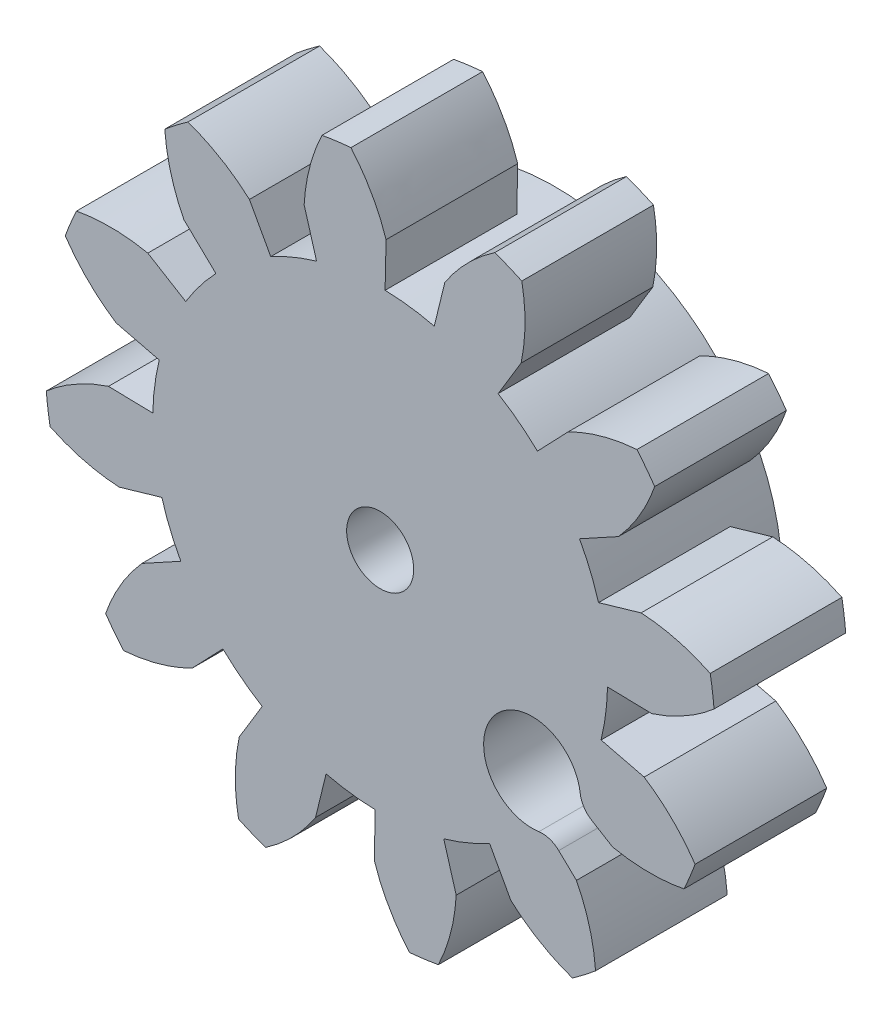
SolidWorks part; units mm, degrees
material "ABS"
ref_plane "Front Plane" through (0, 0, 0) normal (0, 0, 1) x (1, 0, 0)
ref_plane "Top Plane" through (0, 0, 0) normal (0, 1, 0) x (1, 0, 0)
ref_plane "Right Plane" through (0, 0, 0) normal (1, 0, 0) x (0, 0, -1)
sketch "Sketch1" plane through (0, 0, 0) normal (0, 0, 1) x (1, 0, 0)
  line L0 (0, 0) -> (0, 91.8742) construction
  line L1 (-88.8926, 12) -> (81.6756, 12) construction
  line L2 (-69.7625, -13.3915) -> (55.1169, 32.0609) construction
  line L3 (0, 0) -> (-3.8567, 10.5963) construction
  line L4 (0, 0) -> (-11.7377, 89.157) construction
  line L5 (1.5476, 11.1696) -> (0.2461, 11.3499) construction
  line L6 (-8.3652, 7.5617) -> (-1.9324, 14.678) construction
  circle A0 centre (0, 0) radius 12 construction
  circle A1 centre (0, 0) radius 11.2763 construction
  circle A2 centre (0, 0) radius 14 construction
  circle A3 centre (0, 0) radius 9.5 construction
  point P6 (0, 12)
  dimension "D1" = 24
  dimension "D2" = 20
  dimension "D3" = 4.1042
  dimension "D4" = 7.5
  dimension "D5" = 2
  dimension "D6" = 2.5
  dimension "D9" = 9.5929
  dimension "D10" = 1.3139
  dimension "D7" = 5.4886
  dimension "D8" = 5.4886
sketch "Sketch2" plane through (0, 0, 0) normal (0, 0, 1) x (1, 0, 0)
  circle A0 centre (0, 0) radius 9.5 construction
  circle A1 centre (0, 0) radius 9.5
extrude "Gear Body" add sketch "Sketch2" along normal mid plane 5.5
sketch "Sketch3" plane through (0, 0, 0) normal (0, 0, 1) x (1, 0, 0)
  line L0 (0.2461, 11.3499) -> (0, 0) construction
  line L1 (0.2461, 11.3499) -> (0.2059, 9.4978)
  line L4 (-1.9324, 14.678) -> (0, 0) construction
  line L5 (-3.1753, 10.8995) -> (-2.6571, 9.1208)
  circle A2 centre (0, 0) radius 9.5 construction
  arc A3 (0.2059, 9.4978) -> (-2.6571, 9.1208) centre (0, 0) ccw
  spline S0 degree 2 poles (-1.9324, 14.678) (-0.3812, 13.2624) (0.2461, 11.3499) knots 0 0 0 1 1 1
  spline S1 degree 2 poles (-1.9324, 14.678) (-3.0644, 12.9092) (-3.1753, 10.8995) knots 0 0 0 1 1 1
extrude "Gear Tooth" add sketch "Sketch3" along normal mid plane 5.5
pattern_circular "Tooth Pattern" count 12 over 360 about axis through (0, 0, 2.75) along (0, 0, -1) of "Gear Tooth"
sketch "Sketch4" plane through (0, 0, 2.75) normal (0, 0, 1) x (1, 0, 0)
  line L0 (-8.3652, 7.5617) -> (-1.9324, 14.678) construction
  line L1 (-8.3652, 7.5617) -> (-1.9324, 14.678) construction
  circle A0 centre (0, 0) radius 14 construction
  circle A1 centre (0, 0) radius 14
  circle A2 centre (0, 0) radius 14.8047
  point P3 (-1.9324, 14.678)
extrude "Tooth Outer Clean" cut sketch "Sketch4" against normal through all
sketch "Sketch5" plane through (0, 0, 2.75) normal (0, 0, 1) x (1, 0, 0)
  line L0 (0, 0) -> (0, 29.0711) construction
  line L1 (0, 0) -> (-31.2479, 0) construction
  circle A1 centre (0, 0) radius 1.4
  dimension "D2" = 2.8
extrude "Cut-Extrude1" cut sketch "Sketch5" against normal through all
sketch "Sketch7" plane through (0, 0, -2.75) normal (0, 0, -1) x (-1, 0, 0)
  circle A0 centre (0, 0) radius 4.15
  dimension "D1" = 8.3
extrude "Cut-Extrude3" cut sketch "Sketch7" against normal blind 0.2
sketch "Sketch9" plane through (0, 0, -2.75) normal (0, 0, -1) x (-1, 0, 0)
  circle A0 centre (0, 0) radius 9.5
  circle A1 centre (0, 0) radius 4.15 construction
  circle A2 centre (0, 0) radius 4.15
  arc A5 (-4.9272, 8.1223) -> (-6.5703, 6.8615) centre (0, 0) ccw construction
extrude "Boss-Extrude3" add sketch "Sketch9" along normal blind 1.8
sketch "Sketch11" plane through (0, 0, 2.75) normal (0, 0, 1) x (1, 0, 0)
  line L0 (0, 0) -> (0, 16.7253) construction
  line L1 (0, 0) -> (6.3468, -4.8701) construction
  line L2 (0, 0) -> (7.5369, -5.7832) construction
  circle A0 centre (6.3468, -4.8701) radius 1.125
  arc A1 (6.8615, -6.5703) -> (8.1223, -4.9272) centre (0, 0) ccw construction
  dimension "D2" = 2.25
  dimension "D1" = 8
extrude "Cut-Extrude5" cut sketch "Sketch11" against normal through all
sketch "Sketch12" plane through (0, 0, 2.75) normal (0, 0, 1) x (1, 0, 0)
  circle A0 centre (6.3468, -4.8701) radius 2.025
  dimension "D1" = 4.05
extrude "Cut-Extrude6" cut sketch "Sketch12" against normal blind 3.3
fillet "Fillet1" radius 1 2 edges at (8.3617, -5.0724, 1.1) (7.0637, -6.7639, 1.1)
equation "\"Pitch Diameter\"= 24"
equation "\"Diametrical Pitch\"= 0.5"
equation "\"Pressure Angle\"= 20"
equation "\"D1@Sketch1\" = \"Pitch Diameter\""
equation "\"D2@Sketch1\"=\"Pressure Angle\""
equation "\"D4@Sketch1\"=360 / (\"Pitch Diameter\"*\"Diametrical Pitch\")/4"
equation "\"D5@Sketch1\"=1/\"Diametrical Pitch\""
equation "\"D6@Sketch1\"=1.25 / \"Diametrical Pitch\""
equation "\"D9@Sketch1\"=\"D3@Sketch1\"+\"D7@Sketch1\""
equation "\"D10@Sketch1\" = \"D3@Sketch1\" - \"D8@Sketch1\""
equation "\"D8@Sketch1\" = \"D7@Sketch1\""
equation "\"D1@Gear Tooth\"=\"D1@Gear Body\""
equation "\"D1@Tooth Pattern\" = \"Pitch Diameter\" * \"Diametrical Pitch\""
